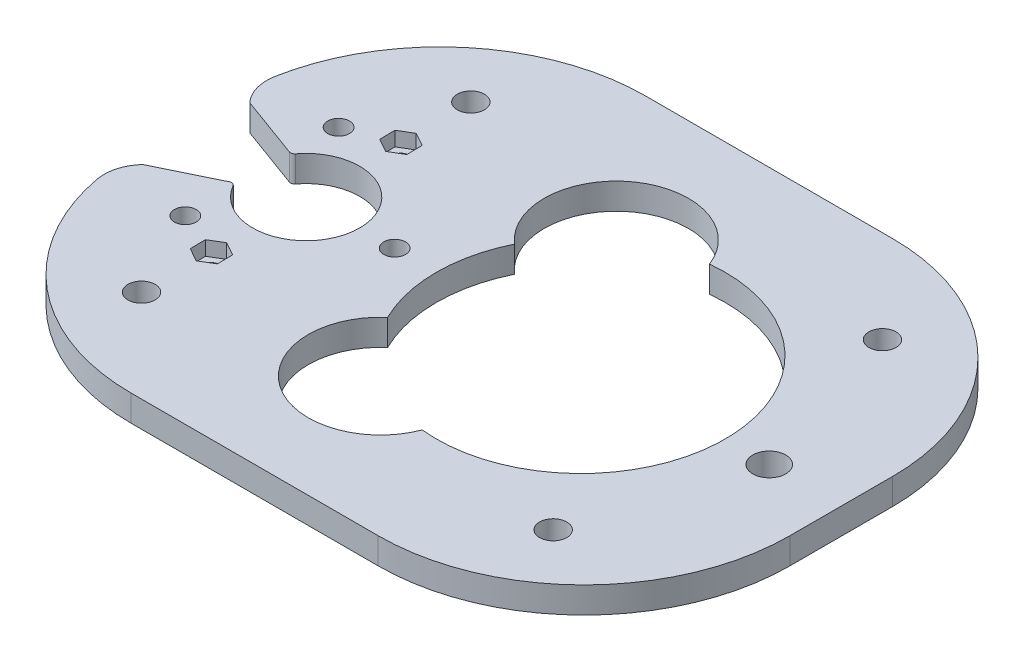
SolidWorks part; units mm, degrees
ref_plane "Front Plane" through (0, 0, 0) normal (0, 0, 1) x (1, 0, 0)
ref_plane "Top Plane" through (0, 0, 0) normal (0, 1, 0) x (1, 0, 0)
ref_plane "Right Plane" through (0, 0, 0) normal (1, 0, 0) x (0, 0, -1)
sketch "Sketch2" plane through (0, 0, 0) normal (0, 1, 0) x (1, 0, 0)
  line L0 (-50, -13) -> (-80, -13)
  line L1 (-80, -62.5) -> (80, -62.5)
  line L2 (-80, -62.5) -> (-80, 62.5)
  line L3 (-80, 62.5) -> (80, 62.5)
  line L4 (80, -62.5) -> (80, 62.5)
  line L5 (-80, -62.5) -> (80, 62.5) construction
  line L6 (-80, 62.5) -> (80, -62.5) construction
  line L7 (-50, 13) -> (-80, 13)
  arc A2 (-20.4423, -2.904) -> (-79.5577, 2.904) centre (-50, 0) ccw
  arc A3 (-79.5577, 2.904) -> (-20.4423, -2.904) centre (-50, 0) ccw
  arc A4 (-20.4423, -2.904) -> (-79.5577, 2.904) centre (-50, 0) ccw
  arc A5 (-79.5577, 2.904) -> (-20.4423, -2.904) centre (-50, 0) ccw
  arc A10 (-46.3072, 22.2455) -> (-49.2928, 22.5389) centre (-47.8, 22.3922) ccw
  arc A11 (-49.2928, 22.5389) -> (-46.3072, 22.2455) centre (-47.8, 22.3922) ccw
  arc A12 (-46.3072, 22.2455) -> (-49.2928, 22.5389) centre (-47.8, 22.3922) ccw construction
  arc A13 (-49.2928, 22.5389) -> (-46.3072, 22.2455) centre (-47.8, 22.3922) ccw construction
  arc A14 (-61.5583, -16.1378) -> (-63.4798, -18.8206) centre (-62.5191, -17.4792) ccw
  arc A15 (-63.4798, -18.8206) -> (-61.5583, -16.1378) centre (-62.5191, -17.4792) ccw
  arc A16 (-61.5583, -16.1378) -> (-63.4798, -18.8206) centre (-62.5191, -17.4792) ccw construction
  arc A17 (-63.4798, -18.8206) -> (-61.5583, -16.1378) centre (-62.5191, -17.4792) ccw construction
  arc A18 (-58.1966, 18.0787) -> (-59.5592, 21.0842) centre (-58.8779, 19.5814) ccw
  arc A19 (-59.5592, 21.0842) -> (-58.1966, 18.0787) centre (-58.8779, 19.5814) ccw
  arc A20 (-58.1966, 18.0787) -> (-59.5592, 21.0842) centre (-58.8779, 19.5814) ccw construction
  arc A21 (-59.5592, 21.0842) -> (-58.1966, 18.0787) centre (-58.8779, 19.5814) ccw construction
  arc A22 (-30.2451, -1.9409) -> (-26.9609, -2.2636) centre (-28.603, -2.1022) ccw
  arc A23 (-26.9609, -2.2636) -> (-30.2451, -1.9409) centre (-28.603, -2.1022) ccw
  arc A24 (-30.2451, -1.9409) -> (-26.9609, -2.2636) centre (-28.603, -2.1022) ccw construction
  arc A25 (-26.9609, -2.2636) -> (-30.2451, -1.9409) centre (-28.603, -2.1022) ccw construction
  arc A26 (-62.9377, 1.2711) -> (-37.0623, -1.2711) centre (-50, 0) ccw
  arc A27 (-37.0623, -1.2711) -> (-62.9377, 1.2711) centre (-50, 0) ccw
  arc A28 (-62.9377, 1.2711) -> (-37.0623, -1.2711) centre (-50, 0) ccw
  arc A29 (-37.0623, -1.2711) -> (-62.9377, 1.2711) centre (-50, 0) ccw
  circle A36 centre (62.5, 0) radius 4
  circle A37 centre (62.5, 0) radius 10.4365
  circle A38 centre (62.5, 0) radius 10.4365
  circle A59 centre (-50, -23.0125) radius 1.435 construction
  circle A60 centre (-50, 23.0125) radius 1.435 construction
  circle A61 centre (-50, -23.0125) radius 1.435 construction
  circle A62 centre (-50, 23.0125) radius 1.435 construction
  point P0 (0, 0)
  dimension "D10" = 8
  dimension "D1" = 160
  dimension "D2" = 125
  dimension "D3" = 0
  dimension "D4" = 0
  dimension "D5" = 0
  dimension "D6" = 0
  dimension "D7" = 0
  dimension "D8" = 0
  dimension "D9" = 0
extrude "Boss-Extrude1" add sketch "Sketch2" along normal blind 6.35 contours A5 L2 L1 L4 L3 A4 | A4 A5 A29 A28 A25 A24 A21 A20 A17 A16 A13 A12 | A38 A36 | A12 A13
fillet "Fillet1" radius 50 4 edges at (80, 3.175, 62.5) (80, 3.175, -62.5) (-80, 3.175, -62.5) (-80, 3.175, 62.5)
hole_wizard "M6 Clearance Hole1" positions "Sketch3" profile "Sketch4" hole size "M6" standard "ANSI Metric"
sketch "Sketch3" plane through (0, 6.35, 0) normal (0, 1, 0) x (1, 0, 0)
  line L1 (-50, -40) -> (50, -40)
  line L2 (-50, -40) -> (-50, 40)
  line L3 (-50, 40) -> (50, 40)
  line L4 (50, -40) -> (50, 40)
  line L5 (-50, -40) -> (50, 40) construction
  line L6 (-50, 40) -> (50, -40) construction
  point P111 (-50, -40)
  point P112 (-50, 40)
  point P134 (50, -40)
  point P137 (50, 40)
  dimension "D1" = 100
  dimension "D2" = 80
  dimension "D3" = 50
  dimension "D4" = 40
sketch "Sketch4" plane through (50, 6.35, -40) normal (1, 0, 0) x (0, 0, 1)
  line L0 (0, 0) -> (0, 16.9828)
  line L1 (0, 16.9828) -> (3.3, 15)
  line L2 (3.3, 15) -> (3.3, 0)
  line L5 (3.3, 0) -> (0, 0)
  line L10 (0, 16.9828) -> (-3.3, 15) construction
  line L11 (0, -6.35) -> (0, 107.95) construction
  dimension "Hole Dia." = 6.6
  dimension "Hole Depth" = 15
  dimension "Drill Angle" = 118
fillet "Fillet2" radius 10 2 edges at (-80, 3.175, 13) (-80, 3.175, -13)
ref_plane "Plane1" through (0, 6.35, 0) normal (0, 1, 0) x (1, 0, 0)
sketch "Sketch5" plane through (0, 6.35, 0) normal (0, 1, 0) x (1, 0, 0)
  line L0 (-50, 0) -> (-28.5, 0) construction
  line L1 (-50, 0) -> (-50, 23.015) construction
  circle A0 centre (-50, 0) radius 13 construction
  circle A1 centre (-50, 0) radius 13 construction
  circle A2 centre (-50, 0) radius 23.015 construction
  circle A3 centre (-50, 0) radius 21.5 construction
  circle A4 centre (-28.5, 0) radius 2.65
  circle A5 centre (-60.75, -18.6195) radius 2.65
  circle A6 centre (-60.75, 18.6195) radius 2.65
  circle A7 centre (-50, 23.015) radius 1.75
  circle A8 centre (-50, -23.015) radius 1.75
  dimension "D1" = 46.03
  dimension "D2" = 43
  dimension "D3" = 5.3
  dimension "D5" = 3.5
  dimension "D4" = 3
  dimension "D6" = 2
extrude "Cut-Extrude1" cut sketch "Sketch5" against normal up to next
sketch "Sketch6" plane through (0, 6.35, 0) normal (0, 1, 0) x (1, 0, 0)
  line L0 (-53.2207, -24.9413) -> (-49.9422, -26.7673)
  line L1 (-46.7793, 24.9413) -> (-50.0578, 26.7673)
  line L2 (-50.0578, 26.7673) -> (-53.2785, 24.8411)
  line L3 (-53.2785, 24.8411) -> (-53.2207, 21.0887)
  line L4 (-53.2207, 21.0887) -> (-49.9422, 19.2627)
  line L5 (-49.9422, 19.2627) -> (-46.7215, 21.1889)
  line L6 (-46.7215, 21.1889) -> (-46.7793, 24.9413)
  line L7 (-49.9422, -26.7673) -> (-46.7215, -24.8411)
  line L8 (-46.7215, -24.8411) -> (-46.7793, -21.0887)
  line L9 (-46.7793, -21.0887) -> (-50.0578, -19.2627)
  line L10 (-50.0578, -19.2627) -> (-53.2785, -21.1889)
  line L11 (-53.2785, -21.1889) -> (-53.2207, -24.9413)
  circle A0 centre (-50, 23.015) radius 1.75 construction
  circle A1 centre (-50, 0) radius 13 construction
  circle A2 centre (-50, 23.015) radius 1.75 construction
  circle A3 centre (-50, 0) radius 13 construction
  circle A4 centre (-50, 23.015) radius 3.25 construction
  dimension "D1" = 6.5
  dimension "D2" = 2
extrude "Cut-Extrude2" cut sketch "Sketch6" against normal blind 3.5
sketch "Sketch7" plane through (0, 6.35, 0) normal (0, 1, 0) x (1, 0, 0)
  line L0 (-76.7037, 13) -> (-60.8237, 7.2006)
  line L1 (-76.7037, -13) -> (-61.6885, -5.6902)
  arc A0 (-76.7037, 13) -> (-76.7037, -13) centre (-50, 0) ccw construction
  arc A1 (-76.7037, 13) -> (-76.7037, -13) centre (-50, 0) ccw
  circle A2 centre (-50, 0) radius 13 construction
  arc A3 (-60.8237, 7.2006) -> (-61.6885, -5.6902) centre (-50, 0) ccw
extrude "Cut-Extrude3" cut sketch "Sketch7" against normal up to next
fillet "Fillet3" radius 1 2 edges at (-61.6885, 3.175, 5.6902) (-60.8237, 3.175, -7.2006)
sketch "Sketch8" plane through (0, 6.35, 0) normal (0, 1, 0) x (1, 0, 0)
  line L0 (16.717, 0) -> (42.3326, 0) construction
  arc A0 (13.0862, -34.8978) -> (13.0862, 34.8978) centre (16.717, 0) ccw
  arc A1 (13.0862, 34.8978) -> (-14.8056, 15.4066) centre (-3.3005, 28.645) ccw
  arc A3 (13.0862, -34.8978) -> (-14.8056, -15.4066) centre (-3.3005, -28.645) cw
  arc A4 (-14.8056, 15.4066) -> (-14.8056, -15.4066) centre (16.717, 0) ccw
extrude "Cut-Extrude4" cut sketch "Sketch8" against normal up to next
